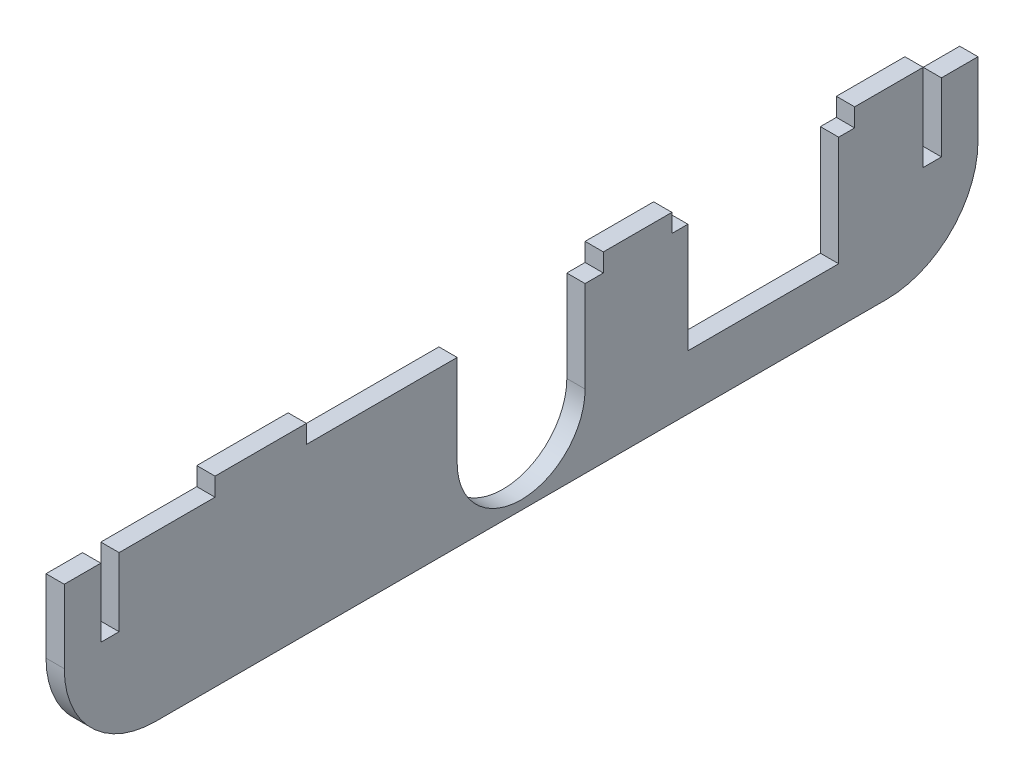
SolidWorks part; units mm, degrees
ref_plane "Front Plane" through (0, 0, 0) normal (0, 0, 1) x (1, 0, 0)
ref_plane "Top Plane" through (0, 0, 0) normal (0, 1, 0) x (1, 0, 0)
ref_plane "Right Plane" through (0, 0, 0) normal (1, 0, 0) x (0, 0, -1)
sketch "Sketch1" plane through (0, 0, 0) normal (1, 0, 0) x (0, 0, -1)
  line L1 (0, 0) -> (254, 0)
  line L2 (0, 0) -> (0, 45.72)
  line L3 (0, 45.72) -> (254, 45.72)
  line L4 (254, 0) -> (254, 45.72)
  dimension "D1" = 254
  dimension "D2" = 45.72
extrude "Boss-Extrude1" add sketch "Sketch1" along normal blind 5.08
sketch "Sketch2" plane through (5.08, 0, 0) normal (1, 0, 0) x (0, 0, -1)
  line L0 (127, 45.72) -> (127, 20.32) construction
  line L2 (254, 45.72) -> (0, 45.72) construction
  circle A1 centre (127, 20.32) radius 17.78
  dimension "D1" = 25.4
  dimension "D2" = 35.56
extrude "Cut-Extrude2" cut sketch "Sketch2" against normal through all
sketch "Sketch4" plane through (5.08, 0, 0) normal (1, 0, 0) x (0, 0, -1)
  line L0 (127, 45.72) -> (127, 38.1) construction
  line L1 (254, 45.72) -> (0, 45.72) construction
  line L2 (109.22, 20.32) -> (109.22, 45.72)
  line L3 (109.22, 45.72) -> (127, 45.72)
  line L4 (144.78, 20.32) -> (144.78, 45.72)
  line L5 (144.78, 45.72) -> (127, 45.72)
  line L6 (109.22, 20.32) -> (144.78, 20.32)
  circle A0 centre (127, 20.32) radius 17.78 construction
extrude "Cut-Extrude3" cut sketch "Sketch4" against normal through all
fillet "Fillet1" radius 25.4 2 edges at (2.54, 0, -254) (2.54, 0, 0)
sketch "Sketch5" plane through (0, 45.72, 0) normal (0, 1, 0) x (1, 0, 0)
  line L0 (0, 54.61) -> (5.08, 54.61) construction
  line L1 (0, 109.22) -> (0, 0) construction
  line L2 (5.08, 109.22) -> (5.08, 0) construction
  line L3 (2.54, 54.61) -> (2.54, 0) construction
  line L4 (5.08, 41.91) -> (0, 41.91)
  line L5 (5.08, 41.91) -> (5.08, 67.31)
  line L6 (5.08, 67.31) -> (0, 67.31)
  line L7 (0, 41.91) -> (0, 67.31)
  line L8 (5.08, 41.91) -> (0, 67.31) construction
  line L9 (5.08, 67.31) -> (0, 41.91) construction
  line L10 (5.08, 0) -> (0, 0) construction
  point P6 (2.54, 54.61)
  dimension "D1" = 25.4
extrude "Boss-Extrude2" add sketch "Sketch5" along normal blind 5.08
sketch "Sketch7" plane through (5.08, 0, 0) normal (1, 0, 0) x (0, 0, -1)
  line L0 (0, 45.72) -> (12.7, 45.72) construction
  line L1 (41.91, 45.72) -> (0, 45.72) construction
  line L2 (12.7, 45.72) -> (12.7, 36.195) construction
  line L4 (10.16, 26.67) -> (15.24, 26.67)
  line L5 (10.16, 26.67) -> (10.16, 45.72)
  line L6 (10.16, 45.72) -> (15.24, 45.72)
  line L7 (15.24, 26.67) -> (15.24, 45.72)
  line L8 (10.16, 26.67) -> (15.24, 45.72) construction
  line L9 (10.16, 45.72) -> (15.24, 26.67) construction
  dimension "D2" = 9.525
  dimension "D3" = 5.08
extrude "Cut-Extrude4" cut sketch "Sketch7" against normal blind 31.75
ref_axis "Axis1" through (0, 2.54, -127) along (1, 0, 0)
ref_plane "Plane1" through (0, 0, -127) normal (0, 0, 1) x (1, 0, 0)
mirror "Mirror1" about plane through (0, 0, -127) normal (0, 0, 1) of "Cut-Extrude4"
sketch "Sketch9" plane through (0, 45.72, 0) normal (0, 1, 0) x (1, 0, 0)
  line L0 (5.08, 238.76) -> (5.08, 144.78) construction
  line L1 (0, 238.76) -> (5.08, 238.76)
  line L2 (0, 238.76) -> (0, 219.71)
  line L3 (0, 219.71) -> (5.08, 219.71)
  line L4 (5.08, 238.76) -> (5.08, 219.71)
  line L5 (0, 238.76) -> (0, 144.78) construction
  line L6 (0, 168.91) -> (5.08, 168.91)
  line L7 (0, 168.91) -> (0, 149.86)
  line L8 (0, 149.86) -> (5.08, 149.86)
  line L9 (5.08, 168.91) -> (5.08, 149.86)
  line L10 (0, 168.91) -> (0, 219.71) construction
  dimension "D1" = 19.05
  dimension "D2" = 50.8
extrude "Boss-Extrude3" add sketch "Sketch9" along normal blind 5.08
sketch "Sketch10" plane through (5.08, 0, 0) normal (1, 0, 0) x (0, 0, -1)
  line L0 (194.31, 45.72) -> (194.31, 30.48) construction
  line L1 (219.71, 45.72) -> (168.91, 45.72) construction
  line L3 (173.355, 15.24) -> (215.265, 15.24)
  line L4 (173.355, 15.24) -> (173.355, 45.72)
  line L5 (173.355, 45.72) -> (215.265, 45.72)
  line L6 (215.265, 15.24) -> (215.265, 45.72)
  line L7 (173.355, 15.24) -> (215.265, 45.72) construction
  line L8 (173.355, 45.72) -> (215.265, 15.24) construction
  dimension "D1" = 30.48
  dimension "D2" = 41.91
extrude "Cut-Extrude6" cut sketch "Sketch10" against normal through all
equation "\"Foamcore\" = .1in"
equation "\"MDF\" = .2in"
equation "\"Gmaterial\"= \"MDF\""
equation "\"PVC-ID\" = \"1.590in\""
equation "\"PVC-OD\" = \"1.900in\""
equation "\"D1@Boss-Extrude1\"=\"Gmaterial\""
equation "\"D1@Boss-Extrude2\"=\"Gmaterial\""
equation "\"D3@Sketch7\"=\"Gmaterial\""
equation "\"D1@Boss-Extrude3\"=\"Gmaterial\""
